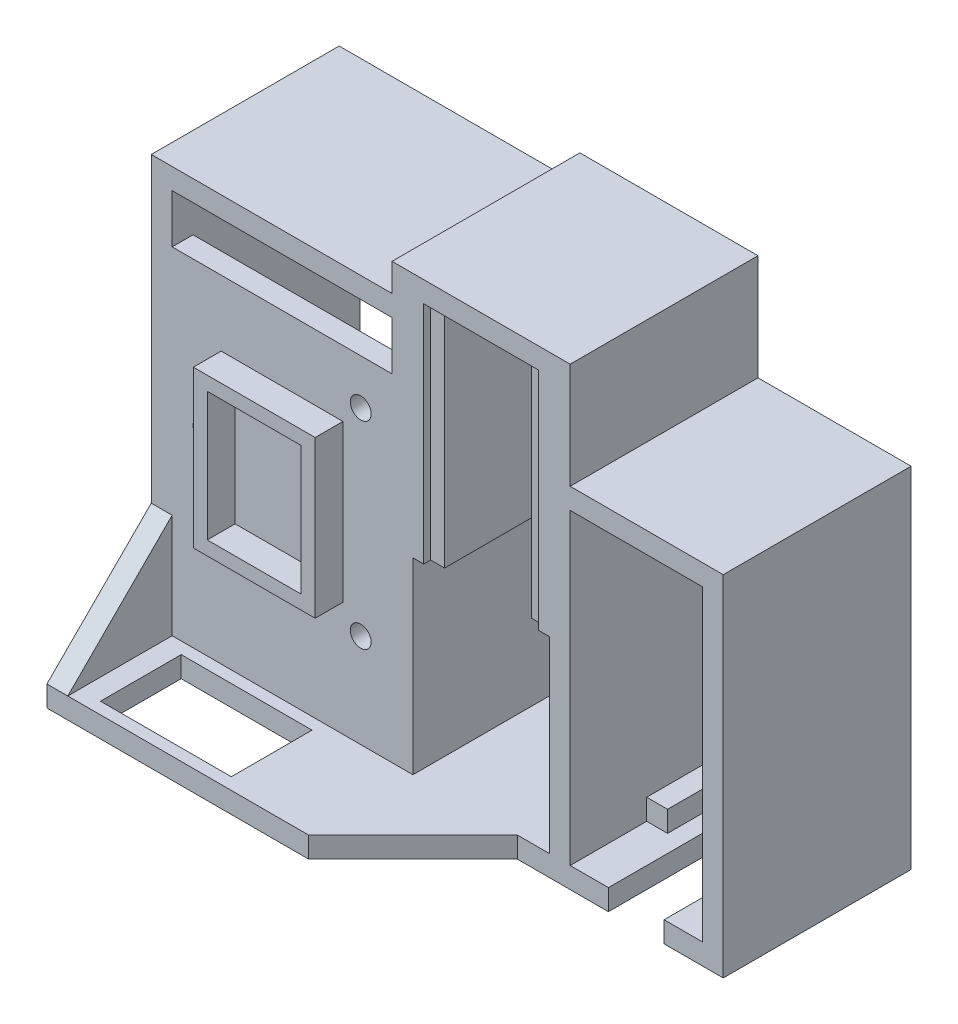
SolidWorks part; units mm, degrees
note: The reader was unsure of these and kept them because the rebuilt part matched: shared geometry of "Sketch1<3>", "Sketch1<4>", "Sketch1<5>", "Sketch1<6>".
ref_plane "Front Plane" through (0, 0, 0) normal (0, 0, 1) x (1, 0, 0)
ref_plane "Top Plane" through (0, 0, 0) normal (0, 1, 0) x (1, 0, 0)
ref_plane "Right Plane" through (0, 0, 0) normal (1, 0, 0) x (0, 0, -1)
sketch "Sketch1" plane through (0, 0, 0) normal (0, 0, 1) x (1, 0, 0)
  line L0 (0, 0) -> (19, 0)
  line L1 (19, 0) -> (16, 0)
  line L2 (0, 0) -> (3, 0)
  line L3 (3, 0) -> (3, 3)
  line L4 (3, 3) -> (0, 3)
  line L5 (0, 3) -> (0, 0)
  line L6 (19, 0) -> (19, 3)
  line L7 (19, 3) -> (16, 3)
  line L8 (16, 3) -> (16, 0)
  line L9 (19, 0) -> (19, 44.2)
  line L10 (19, 44.2) -> (14, 44.2)
  line L11 (14, 44.2) -> (14, 41.2)
  line L12 (14, 41.2) -> (19, 41.2)
  line L13 (14, 44.2) -> (0, 44.2)
  line L14 (0, 44.2) -> (0, 41.2)
  line L15 (0, 41.2) -> (5, 41.2)
  line L16 (5, 41.2) -> (5, 44.2)
  line L17 (0, 41.2) -> (0, 3)
  line L18 (19, 0) -> (22, 0)
  line L19 (22, 0) -> (22, -3)
  line L20 (22, -3) -> (0, -3)
  line L21 (22, 0) -> (22, 44.2)
  line L22 (22, 44.2) -> (22, 47.2)
  line L23 (22, 47.2) -> (0, 47.2)
  line L24 (0, 47.2) -> (0, 44.2)
  line L25 (0, -3) -> (-25.6, -3)
  line L26 (0, 0) -> (-3, 0)
  line L27 (-3, 0) -> (-3, 27)
  line L28 (-3, 27) -> (-4.55, 27)
  line L29 (-4.55, 27) -> (-4.55, 59.4)
  line L30 (-4.55, 59.4) -> (-21.05, 59.4)
  line L31 (-21.05, 59.4) -> (-21.05, 27)
  line L32 (-21.05, 27) -> (-22.6, 27)
  line L33 (-25.6, -3) -> (-25.6, 27)
  line L34 (-25.6, 27) -> (-22.6, 27)
  line L35 (-22.6, 27) -> (-22.6, 0)
  line L36 (-22.6, 0) -> (-3, 0)
  line L37 (-25.6, 27) -> (-25.6, 59.4)
  line L38 (-25.6, 59.4) -> (-25.6, 62.4)
  line L39 (-25.6, 62.4) -> (-4.55, 62.4)
  line L40 (-4.55, 62.4) -> (0, 62.4)
  line L41 (0, 62.4) -> (0, 47.2)
  line L42 (-21.05, 27) -> (-19.05, 27)
  line L43 (-19.05, 27) -> (-19.05, 59.4)
  line L44 (-4.55, 27) -> (-6.55, 27)
  line L45 (-6.55, 27) -> (-6.55, 59.4)
  line L46 (0, -3) -> (5.5, -3)
  line L47 (5.5, -3) -> (5.5, 0)
  line L48 (5.5, 0) -> (13.5, 0)
  line L49 (13.5, 0) -> (13.5, -3)
  dimension "D1" = 19
  dimension "D2" = 3
  dimension "D3" = 3
  dimension "D4" = 22
  dimension "D5" = 25.6
extrude "Boss-Extrude1" add sketch "Sketch1" along normal blind 3 contours L20 L47 L0 L26 L36 L35 L34 L33 L25 | L41 L40 L39 L38 L37 L34 L32 L31 L30 L29 L28 L27 L26 L5 L17 L14 L24 | L42 L43 L30 L31 | L44 L45 L30 L43 L42 L32 L35 L36 L27 L28 | L15 L16 L13 L14 | L23 L24 L13 L10 L9 L6 L18 L21 L22 | L11 L12 L9 L10 | L15 L17 L4 L3 L0 L8 L7 L9 L12 L11 L13 L16 | L7 L8 L0 L6 | L0 L49 L20 L19 L18 | L4 L5 L0 L3 | L49 L0 L47 L20 | L45 L44 L29 L30
extrude "Boss-Extrude2" add sketch "Sketch1<3>" along normal blind 27 contours L41 L40 L39 L38 L37 L34 L32 L31 L30 L29 L28 L27 L26 L5 L17 L14 L24 | L20 L47 L0 L26 L36 L35 L34 L33 L25 | L0 L49 L20 L19 L18 | L23 L24 L13 L10 L9 L6 L18 L21 L22
sketch "Sketch1<3>" plane through (0, 0, 0) normal (0, 0, 1) x (1, 0, 0) same geometry as "Sketch1"
extrude "Boss-Extrude3" add sketch "Sketch1<4>" along normal blind 16 contours L15 L16 L13 L14 | L11 L12 L9 L10 | L7 L8 L0 L6 | L4 L5 L0 L3
sketch "Sketch1<4>" plane through (0, 0, 0) normal (0, 0, 1) x (1, 0, 0) same geometry as "Sketch1"
extrude "Boss-Extrude4" add sketch "Sketch1<5>" along normal blind 11 contours L49 L0 L47 L20
sketch "Sketch1<5>" plane through (0, 0, 0) normal (0, 0, 1) x (1, 0, 0) same geometry as "Sketch1"
extrude "Boss-Extrude5" add sketch "Sketch1<6>" along normal blind 26 contours L45 L44 L29 L30 | L42 L43 L30 L31
sketch "Sketch1<6>" plane through (0, 0, 0) normal (0, 0, 1) x (1, 0, 0) same geometry as "Sketch1"
sketch "Sketch2" plane through (0, 0, 0) normal (0, 0, -1) x (-1, 0, 0)
  line L0 (25.6, -3) -> (60.2, -3)
  line L1 (60.2, -3) -> (60.2, 58.4)
  line L2 (60.2, 58.4) -> (25.6, 58.4)
  line L3 (25.6, -3) -> (25.6, 62.4) construction
  line L4 (25.6, 58.4) -> (25.6, -3)
  line L5 (25.6, 0) -> (57.2, 0)
  line L6 (57.2, 0) -> (57.2, 55.4)
  line L7 (57.2, 55.4) -> (25.6, 55.4)
  line L8 (25.6, 55.4) -> (25.6, 48.4)
  line L9 (25.6, 48.4) -> (57.2, 48.4)
  line M11 (25.6, -3) -> (25.6, 62.4)
extrude "Boss-Extrude6" add sketch "Sketch2" against normal blind 27 contours L9 L6 L7 M11 | L9 L4 L5 L6
sketch "Sketch3" plane through (0, 0, 27) normal (0, 0, 1) x (1, 0, 0)
  line L0 (-25.6, 0) -> (-57.2, 0)
  line L1 (-25.6, 0) -> (-57.2, 0) construction
  line L2 (-57.2, 0) -> (-57.2, 55.4)
  line L3 (-57.2, 55.4) -> (-25.6, 55.4)
  line L4 (-25.6, 55.4) -> (-25.6, 0)
  line L7 (-25.6, 48.4) -> (-57.2, 48.4)
  line M7 (-25.6, 0) -> (-57.2, 0)
  line M8 (-57.2, 0) -> (-57.2, 55.4)
extrude "Boss-Extrude7" add sketch "Sketch3" against normal blind 3 contours L4 L7 M8 M7
sketch "Sketch4" plane through (0, -3, 0) normal (0, -1, 0) x (-1, 0, 0)
  line L0 (22.6, -27) -> (22.6, -42)
  line L1 (22.6, -42) -> (60.2, -42)
  line L2 (60.2, -42) -> (60.2, -27)
  line L3 (60.2, -27) -> (22.6, -27)
  line L4 (22.6, -42) -> (7.6, -27)
  line L5 (60.2, -32.9917) -> (54.2, -32.9917)
  line L6 (-5.5, -27) -> (60.2, -27) construction
  line L7 (7.6, -27) -> (22.6, -27)
  line L8 (53.328, -27) -> (53.328, -28.7)
  line L9 (54.2, -32.9917) -> (54.2, -28.7)
  line L10 (54.2, -28.7) -> (35.4, -28.7)
  line L11 (35.4, -28.7) -> (35.4, -40.3)
  line L12 (35.4, -40.3) -> (54.2, -40.3)
  line L13 (54.2, -40.3) -> (54.2, -32.9917)
  line M10 (-5.5, -27) -> (60.2, -27)
  dimension "D1" = 1.7
extrude "Boss-Extrude8" add sketch "Sketch4" against normal blind 3 contours L4 L0 M10 | L13 L12 L11 L10 L8 L0 L1 L2 L5 M10 | L10 L9 L5 L2 L3 L8
sketch "Sketch5" plane through (-60.2, 0, 0) normal (-1, 0, 0) x (0, 0, 1)
  line L0 (27, 0) -> (42, 0)
  line L1 (42, 0) -> (27, 15)
  line L2 (27, 0) -> (27, 58.4) construction
  line L3 (27, 15) -> (27, 0)
extrude "Boss-Extrude9" add sketch "Sketch5" against normal blind 3
sketch "Sketch6" plane through (0, 0, 24) normal (0, 0, -1) x (-1, 0, 0)
  line L0 (57.2, 27.7) -> (52.7, 27.7)
  line L1 (57.2, 0) -> (57.2, 55.4) construction
  line L2 (25.6, 1.0831) -> (30.1, 1.0831)
  line L3 (25.6, 0) -> (25.6, 55.4) construction
  line L4 (30.1, 0) -> (30.1, 13.5)
  line L5 (25.6, 0) -> (57.2, 0) construction
  line L6 (30.1, 55.4) -> (30.1, 41.9)
  line L7 (57.2, 55.4) -> (25.6, 55.4) construction
  circle A0 centre (30.1, 41.9) radius 1.5
  circle A1 centre (30.1, 13.5) radius 1.5
  circle A2 centre (52.7, 27.7) radius 1.5
extrude "Cut-Extrude1" cut sketch "Sketch6" against normal blind 10
sketch "Sketch7" plane through (0, 0, 27) normal (0, 0, 1) x (1, 0, 0)
  line L0 (-52.7, 27.7) -> (-30.1, 27.7)
  line L1 (-41.4, 27.7) -> (-41.4, 18.45)
  line L2 (-41.4, 27.7) -> (-41.4, 36.95)
  line L3 (-41.4, 36.95) -> (-48.15, 36.95)
  line L4 (-48.15, 36.95) -> (-48.15, 18.45)
  line L5 (-48.15, 18.45) -> (-34.65, 18.45)
  line L6 (-34.65, 18.45) -> (-34.65, 36.95)
  line L7 (-34.65, 36.95) -> (-41.4, 36.95)
  line L8 (-34.65, 18.45) -> (-32.65, 18.45)
  line L9 (-32.65, 18.45) -> (-32.65, 36.95)
  line L10 (-32.65, 36.95) -> (-32.65, 38.95)
  line L11 (-32.65, 38.95) -> (-48.15, 38.95)
  line L12 (-48.15, 38.95) -> (-50.15, 38.95)
  line L13 (-50.15, 38.95) -> (-50.15, 18.45)
  line L14 (-50.15, 18.45) -> (-50.15, 16.45)
  line L15 (-50.15, 16.45) -> (-32.65, 16.45)
  line L16 (-32.65, 16.45) -> (-32.65, 18.45)
  dimension "D1" = 15.5
  dimension "D2" = 2
  dimension "D3" = 18.5
  dimension "D4" = 2
  dimension "D5" = 20.5
extrude "Boss-Extrude10" add sketch "Sketch7" along normal blind 4 contours L12 L13 L0 L4 L3 L7 L6 L9 L10 L11 | L15 L16 L8 L5 L4 L0 L13 L14 | L8 L9 L0 L6
